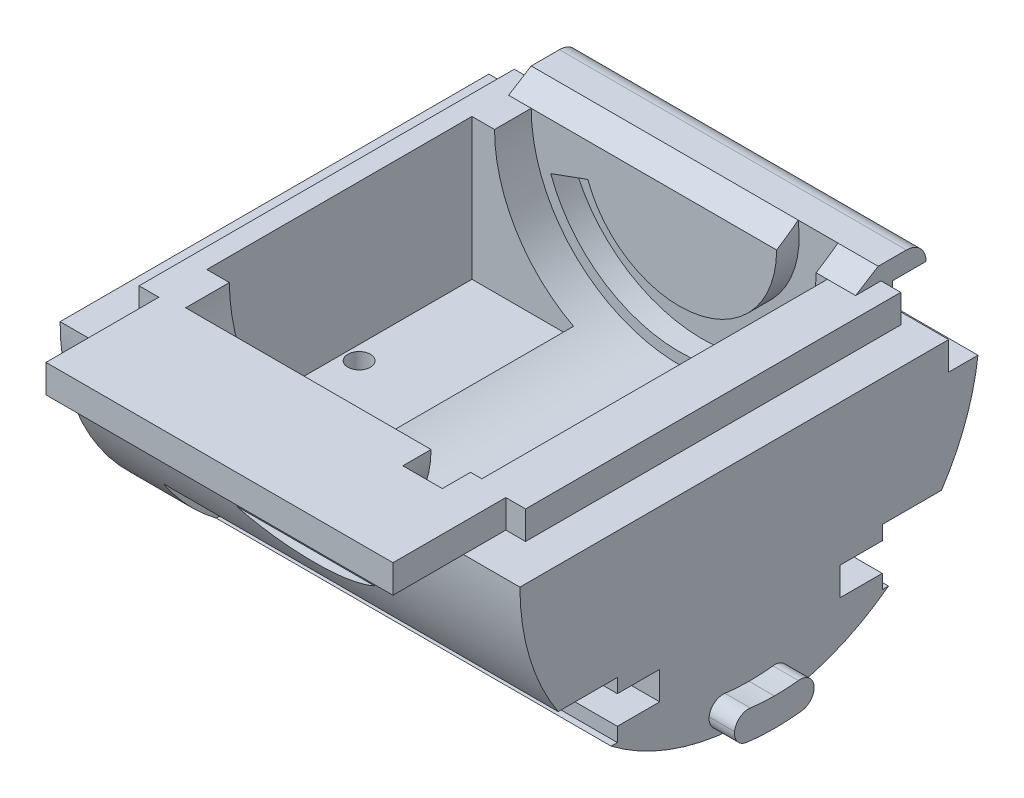
SolidWorks part; units mm, degrees
ref_plane "Front Plane" through (0, 0, 0) normal (0, 0, 1) x (1, 0, 0)
ref_plane "Top Plane" through (0, 0, 0) normal (0, 1, 0) x (1, 0, 0)
ref_plane "Right Plane" through (0, 0, 0) normal (1, 0, 0) x (0, 0, -1)
sketch "Sketch1" plane through (0, 0, 0) normal (0, 1, 0) x (1, 0, 0)
  line L1 (0, 0) -> (41.402, 0)
  line L2 (0, 0) -> (0, -21.971)
  line L3 (0, -21.971) -> (41.402, -21.971)
  line L4 (41.402, 0) -> (41.402, -21.971)
  dimension "D1" = 21.971
  dimension "D2" = 41.402
revolve "Revolve1" add sketch "Sketch1" angle 180 about L1
sketch "Sketch2" plane through (0, 0, 0) normal (0, 1, 0) x (1, 0, 0)
  line L0 (0, 21.971) -> (41.402, 21.971) construction
  line L1 (5.08, 17.145) -> (36.322, 17.145)
  line L2 (5.08, 17.145) -> (5.08, -23.749)
  line L3 (5.08, -23.749) -> (36.322, -23.749)
  line L4 (36.322, 17.145) -> (36.322, -23.749)
  line L6 (41.402, 21.971) -> (41.402, -21.971) construction
  line L7 (0, -21.971) -> (0, 21.971) construction
  line L11 (0, -21.971) -> (41.402, -21.971) construction
  dimension "D1" = 5.08
  dimension "D2" = 5.08
  dimension "D3" = 4.826
  dimension "D4" = 1.778
extrude "Boss-Extrude1" add sketch "Sketch2" along normal blind 2.54
sketch "Sketch3" plane through (0, 2.54, 0) normal (0, 1, 0) x (1, 0, 0)
  line L2 (5.08, 17.145) -> (5.08, -23.749) construction
  line L3 (36.322, -23.749) -> (36.322, 17.145) construction
  line L4 (20.447, 14.605) -> (20.447, -16.51) construction
  line L5 (20.447, 14.605) -> (33.782, 14.605)
  line L6 (33.782, -16.51) -> (20.447, -16.51)
  line L7 (20.447, 14.605) -> (20.447, -16.51)
  line L8 (36.322, 17.145) -> (5.08, 17.145) construction
  line L9 (0, -21.971) -> (5.08, -21.971) construction
  line L12 (7.62, 14.605) -> (7.62, -16.51)
  line L13 (7.62, -16.51) -> (33.782, -16.51)
  line L14 (33.782, -16.51) -> (33.782, 14.605)
  line L15 (33.782, 14.605) -> (7.62, 14.605)
  dimension "D2" = 13.335
  dimension "D1" = 5.461
  dimension "D3" = 2.54
  dimension "D4" = 2.54
  dimension "D5" = 2.54
revolve "Cut-Revolve2" cut sketch "Sketch3" angle 360 about L4
sketch3d "3DSketch1" plane through (0, 0, 0) normal (0, 0, 1) x (1, 0, 0)
  dimension "D1" = 15.875
sketch "Sketch7" plane through (0, 0, -17.145) normal (0, 0, -1) x (-1, 0, 0)
  line L1 (-36.322, 2.54) -> (-5.08, 2.54)
  line L2 (-36.322, 2.54) -> (-36.322, 1.27)
  line L3 (-36.322, 1.27) -> (-5.08, 1.27)
  line L4 (-5.08, 2.54) -> (-5.08, 1.27)
  dimension "D1" = 1.27
extrude "Boss-Extrude5" add sketch "Sketch7" along normal blind 3.81
sketch "Sketch8" plane through (0, 0, 0) normal (0, 1, 0) x (1, 0, 0)
  line L1 (42.164, 20.447) -> (0, 20.447)
  line L2 (42.164, 20.447) -> (42.164, 17.907)
  line L3 (42.164, 17.907) -> (0, 17.907)
  line L4 (0, 20.447) -> (0, 17.907)
  line L5 (36.322, 17.145) -> (5.08, 17.145) construction
  line L7 (36.322, -21.971) -> (36.322, 17.145) construction
  line L8 (0, -21.971) -> (0, 21.971) construction
  dimension "D1" = 5.842
  dimension "D2" = 2.54
  dimension "D3" = 0.762
extrude "Cut-Extrude1" cut sketch "Sketch8" against normal blind 2.54
sketch "Sketch9" plane through (0, 2.54, 0) normal (0, 1, 0) x (1, 0, 0)
  line L0 (5.1158, -6.35) -> (26.6447, -6.35) construction
  line L1 (7.112, -16.51) -> (29.21, -16.51) construction
  line L2 (7.112, 14.605) -> (33.782, 14.605) construction
  line L3 (32.766, 16.637) -> (29.21, 16.637)
  line L4 (32.766, 16.637) -> (32.766, -19.05)
  line L5 (32.766, -19.05) -> (29.21, -19.05)
  line L6 (29.21, 16.637) -> (29.21, -19.05)
  line L7 (36.322, -21.971) -> (36.322, -16.891) construction
  line L8 (20.447, 14.605) -> (20.447, -16.51) construction
  line L9 (33.782, 14.605) -> (32.766, 14.605) construction
  line L11 (0, -21.971) -> (5.08, -21.971) construction
  dimension "D1" = 15.621
  dimension "D2" = 2.54
  dimension "D3" = 2.032
  dimension "D4" = 3.556
  dimension "D5" = 3.556
sketch "Sketch10" plane through (36.322, 0, 0) normal (1, 0, 0) x (0, 0, -1)
  line L0 (-23.749, 2.54) -> (20.955, 2.54) construction
  line L1 (16.891, 0) -> (-16.891, 0)
  line L2 (16.891, 0) -> (16.891, 2.54)
  line L3 (16.891, 2.54) -> (-16.891, 2.54)
  line L4 (-16.891, 0) -> (-16.891, 2.54)
  line L5 (-21.971, 0) -> (17.145, 0) construction
  dimension "D1" = 5.08
  dimension "D2" = 5.08
extrude "Boss-Extrude6" add sketch "Sketch10" along normal blind 1.778
sketch "Sketch13" plane through (0, 2.54, 0) normal (0, 1, 0) x (1, 0, 0)
  line L0 (7.112, -16.51) -> (33.782, -16.51) construction
  line L1 (14.224, -12.573) -> (5.08, -12.573)
  line L2 (14.224, -12.573) -> (14.224, 11.303)
  line L3 (14.224, 11.303) -> (5.08, 11.303)
  line L4 (5.08, -12.573) -> (5.08, 11.303)
  line L5 (33.782, 14.605) -> (7.112, 14.605) construction
  line L7 (5.08, 20.955) -> (5.08, -23.749) construction
  line L8 (7.112, -16.51) -> (7.112, 14.605) construction
  dimension "D1" = 3.937
  dimension "D2" = 3.302
  dimension "D3" = 7.112
sketch "Sketch14" plane through (5.08, 0, 0) normal (-1, 0, 0) x (0, 0, 1)
  line L0 (-20.955, 2.54) -> (23.749, 2.54) construction
  line L1 (-16.891, 2.54) -> (16.891, 2.54)
  line L2 (-16.891, 2.54) -> (-16.891, 0)
  line L3 (-16.891, 0) -> (16.891, 0)
  line L4 (16.891, 2.54) -> (16.891, 0)
  line L5 (16.891, 0) -> (-16.891, 0) construction
  dimension "D1" = 5.08
  dimension "D2" = 5.08
extrude "Boss-Extrude7" add sketch "Sketch14" along normal blind 1.778
extrude "Cut-Extrude3" cut sketch "Sketch13" against normal blind 12.7
sketch "Sketch15" plane through (0, -10.16, 0) normal (0, 1, 0) x (1, 0, 0)
  line L0 (5.08, -12.573) -> (14.224, -12.573) construction
  line L1 (26.037, -12.573) -> (25.021, -12.573)
  line L2 (26.037, -12.573) -> (26.037, 11.303)
  line L3 (26.037, 11.303) -> (25.021, 11.303)
  line L4 (25.021, -12.573) -> (25.021, 11.303)
  line L5 (14.224, 11.303) -> (5.08, 11.303) construction
  line L7 (24.513, 11.303) -> (24.513, -12.573) construction
  dimension "D1" = 0.508
  dimension "D2" = 1.016
sketch "Sketch16" plane through (0, -10.16, 0) normal (0, 1, 0) x (1, 0, 0)
  line L1 (5.08, 11.303) -> (5.08, -12.573) construction
  line L3 (14.224, 11.303) -> (5.08, 11.303) construction
  circle A0 centre (6.35, -0.127) radius 1.016
  dimension "D3" = 2.032
  dimension "D1" = 11.43
  dimension "D2" = 1.27
extrude "Cut-Extrude4" cut sketch "Sketch16" against normal blind 2.54
sketch "Sketch18" plane through (41.402, 0, 0) normal (1, 0, 0) x (0, 0, -1)
  circle A0 centre (-0.0842, -18.9242) radius 1.27
  arc A1 (-21.971, 0) -> (21.971, 0) centre (0, 0) ccw construction
  point P5 (0, -21.971)
  dimension "D2" = 2.54
  dimension "D1" = 3.048
extrude "Boss-Extrude8" add sketch "Sketch18" along normal blind 2.286
sketch "Sketch19" plane through (0, 0, 0) normal (-1, 0, 0) x (0, 0, 1)
  circle A0 centre (0.0842, -18.9242) radius 1.27
  arc A1 (-21.971, 0) -> (21.971, 0) centre (0, 0) ccw construction
  point P5 (0, -21.971)
  dimension "D2" = 2.54
  dimension "D1" = 3.048
extrude "Boss-Extrude9" add sketch "Sketch19" along normal blind 2.286
sketch "Sketch20" plane through (0, 0, -17.145) normal (0, 0, -1) x (-1, 0, 0)
  line L4 (-36.322, 1.27) -> (-36.322, 0)
  line L5 (-36.322, 1.27) -> (-36.322, 0) construction
  line L6 (-36.322, 0) -> (-10.2475, 0)
  line L9 (-10.2475, 0) -> (-5.08, 0)
  line L12 (-5.08, 1.27) -> (-36.322, 1.27)
  line L15 (-5.08, 0) -> (-5.08, 1.27)
extrude "Boss-Extrude10" add sketch "Sketch20" along normal blind 1.27
revolve "Cut-Revolve5" cut sketch "Sketch9" angle 160 about L8 other way angle 160
sketch "x" plane through (43.688, 0, 0) normal (1, 0, 0) x (0, 0, -1)
  line L0 (3.3756, -17.3286) -> (3.6066, -19.8697)
  line L1 (-3.5297, -17.2979) -> (-3.7833, -19.8368)
  arc A0 (-0.0842, -20.1942) -> (3.6066, -19.8697) centre (0, 0) ccw
  circle A1 centre (-0.0842, -18.9242) radius 1.27 construction
  arc A2 (-0.0842, -20.1942) -> (-3.7833, -19.8368) centre (0, 0) cw
  arc A3 (-0.0842, -17.6542) -> (-3.5297, -17.2979) centre (0, 0) cw
  arc A4 (-0.0842, -17.6542) -> (3.3756, -17.3286) centre (0, 0) ccw
  dimension "D1" = 3.81
  dimension "D2" = 3.81
  dimension "D3" = 3.81
  dimension "D4" = 3.81
extrude "Boss-Extrude11" add sketch "x" against normal blind 8.382
sketch "Sketch22" plane through (-2.286, 0, 0) normal (-1, 0, 0) x (0, 0, 1)
  line L0 (-3.3756, -17.3286) -> (-3.6066, -19.8697)
  line L1 (3.7833, -19.8368) -> (3.5297, -17.2979)
  arc A0 (0.0842, -17.6542) -> (3.5297, -17.2979) centre (0, 0) ccw
  circle A1 centre (0.0842, -18.9242) radius 1.27 construction
  arc A2 (0.0842, -17.6542) -> (-3.3756, -17.3286) centre (0, 0) cw
  arc A3 (0.0842, -20.1942) -> (3.7833, -19.8368) centre (0, 0) ccw
  arc A4 (0.0842, -20.1942) -> (-3.6066, -19.8697) centre (0, 0) cw
  dimension "D1" = 3.81
  dimension "D2" = 3.81
  dimension "D3" = 3.81
  dimension "D4" = 3.81
extrude "Boss-Extrude12" add sketch "Sketch22" against normal blind 14.224
fillet "Fillet4" radius 1.27 9 edges at (-1.143, -17.3286, -3.3756) (-1.143, -19.8697, -3.6066) (-1.143, -17.2979, 3.5297) (42.545, -19.8368, 3.7833) (42.545, -17.2979, 3.5297) (42.545, -19.8697, -3.6066) (42.545, -17.3286, -3.3756) (42.545, -17.6542, 0.0729) (-1.143, -19.8368, 3.7833)
sketch "Sketch24" plane through (0, 2.54, 0) normal (0, 1, 0) x (1, 0, 0)
  line L0 (29.21, 16.637) -> (32.766, 16.637) construction
  line L1 (36.322, 20.955) -> (5.08, 20.955)
  line L2 (36.322, 20.955) -> (36.322, 16.637)
  line L3 (36.322, 16.637) -> (5.08, 16.637)
  line L4 (5.08, 20.955) -> (5.08, 16.637)
  dimension "D1" = 0
extrude "Boss-Extrude13" add sketch "Sketch24" along normal blind 1.27
sketch "Sketch23" plane through (36.322, 0, 0) normal (1, 0, 0) x (0, 0, -1)
  line L0 (17.907, 0) -> (17.907, -2.54) construction
  line L1 (18.415, 0) -> (17.907, 0)
  line L2 (18.415, 0) -> (18.415, 1.27)
  line L4 (17.907, 0) -> (17.907, 1.27)
  line L6 (17.907, 1.27) -> (17.907, 2.032)
  line L7 (17.907, 2.032) -> (20.955, 2.032)
  line L8 (20.955, 3.81) -> (20.955, 1.27) construction
  line L9 (20.955, 2.032) -> (20.955, 1.27)
  line L10 (20.955, 1.27) -> (18.415, 1.27)
  dimension "D1" = 0
  dimension "D2" = 0.762
extrude "Cut-Extrude5" cut sketch "Sketch23" against normal blind 40.894
chamfer "Chamfer1" distance 1.27 angle 58 2 edges at (17.145, 2.54, -16.637) (34.544, 2.54, -16.637) first distance on face at (21.1111, -0.1884, -16.637)
fillet "Fillet5" radius 1.778 1 edges at (20.701, 3.81, -20.955)
sketch "Sketch25" plane through (41.402, 0, 0) normal (1, 0, 0) x (0, 0, -1)
  line L1 (20.447, -2.54) -> (17.8567, -2.54)
  line L2 (20.447, -2.54) -> (20.447, 1.778)
  line L3 (20.447, 1.778) -> (17.8567, 1.778)
  line L4 (17.8567, -2.54) -> (17.8567, 1.778)
  line L5 (20.447, 1.778) -> (21.971, 1.778)
  line L6 (20.447, 1.778) -> (20.447, 0)
  line L7 (20.447, 0) -> (21.971, 0)
  line L8 (21.971, 1.778) -> (21.971, 0)
  dimension "D1" = 4.318
  dimension "D2" = 1.778
sketch "Sketch26" plane through (41.402, 0, 0) normal (1, 0, 0) x (0, 0, -1)
  line L0 (21.971, 0) -> (20.447, 0) construction
  line L1 (-21.971, 0) -> (-20.701, 0)
  line L2 (20.701, 0) -> (21.971, 0)
  arc A0 (-21.971, 0) -> (21.971, 0) centre (0, 0) ccw
  arc A1 (-21.971, 0) -> (21.971, 0) centre (0, 0) ccw construction
  arc A2 (-20.701, 0) -> (20.701, 0) centre (0, 0) ccw
  dimension "D1" = 1.27
extrude "Cut-Extrude6" cut sketch "Sketch26" against normal blind 48.26
sketch "Sketch27" plane through (41.402, 0, 0) normal (1, 0, 0) x (0, 0, -1)
  line L0 (-16.891, 0) -> (16.891, 0) construction
  line L1 (-17.2594, -11.43) -> (-11.9254, -11.43)
  line L2 (-17.2594, -11.43) -> (-17.2594, -16.51)
  line L3 (-17.2594, -16.51) -> (-11.9254, -16.51)
  line L4 (-11.9254, -11.43) -> (-11.9254, -12.7)
  line L5 (0, 13.4811) -> (0, -13.4811) construction
  line L6 (17.2594, -16.51) -> (11.9254, -16.51)
  line L7 (11.9254, -11.43) -> (11.9254, -12.7)
  line L8 (17.2594, -11.43) -> (11.9254, -11.43)
  line L9 (17.2594, -11.43) -> (17.2594, -16.51)
  line L10 (-11.9254, -15.24) -> (-11.9254, -16.51)
  line L11 (-11.9254, -12.7) -> (-8.1154, -12.7)
  line L13 (-11.9254, -15.24) -> (-8.1154, -15.24)
  line L14 (-8.1154, -12.7) -> (-8.1154, -15.24)
  line L15 (11.9254, -15.24) -> (11.9254, -16.51)
  line L16 (11.9254, -12.7) -> (8.1154, -12.7)
  line L18 (11.9254, -15.24) -> (8.1154, -15.24)
  line L19 (8.1154, -12.7) -> (8.1154, -15.24)
  arc A0 (-20.701, 0) -> (20.701, 0) centre (0, 0) ccw construction
  dimension "D1" = 5.334
  dimension "D2" = 11.43
  dimension "D3" = 5.08
  dimension "D4" = 2.54
  dimension "D5" = 1.27
  dimension "D6" = 3.81
  dimension "D7" = 3.81
  dimension "D8" = 2.54
  dimension "D9" = 1.27
extrude "Cut-Extrude7" cut sketch "Sketch27" against normal blind 35.56
sketch "Sketch28" plane through (0, -2.54, 0) normal (0, 1, 0) x (1, 0, 0)
  line L0 (41.402, 17.907) -> (41.402, 20.447) construction
  line L1 (41.402, 19.177) -> (0, 19.177)
  line L2 (41.402, 19.177) -> (41.402, 24.7565)
  line L3 (41.402, 24.7565) -> (0, 24.7565)
  line L4 (0, 19.177) -> (0, 24.7565)
extrude "Cut-Extrude8" cut sketch "Sketch28" along normal blind 3.81
ref_axis "Axis1" through (-4.5847, 0, 0) along (1, 0, 0)
ref_plane "Plane1" through (20.701, 0, 0) normal (-1, 0, 0) x (0, 0, 1)
ref_point "Point1"
sketch "Sketch29" plane through (0, 0, 23.749) normal (0, 0, 1) x (1, 0, 0)
  line L8 (5.08, 0) -> (36.322, 0)
  line L9 (36.322, 0) -> (36.322, 2.54)
  line L10 (36.322, 2.54) -> (5.08, 2.54)
  line L11 (5.08, 2.54) -> (5.08, 0)
  line L12 (5.08, 0) -> (36.322, 0)
  line L13 (36.322, 0) -> (36.322, 2.54)
  line L14 (36.322, 2.54) -> (5.08, 2.54)
  line L15 (5.08, 2.54) -> (5.08, 0)
  dimension "D1" = 0
extrude "Boss-Extrude14" add sketch "Sketch29" along normal blind 3.302
